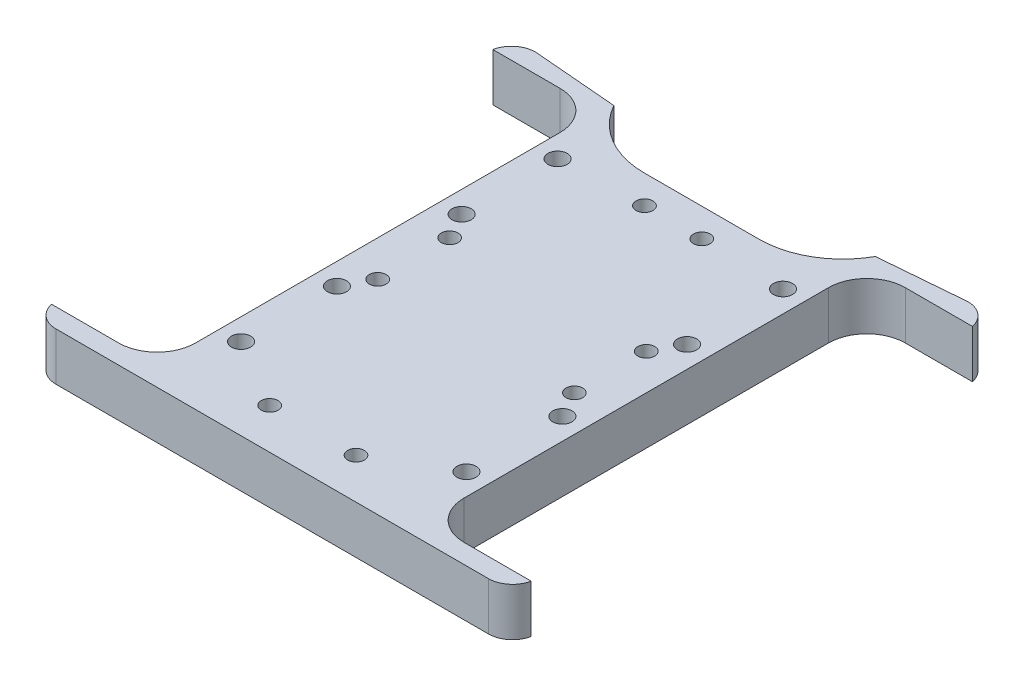
SolidWorks part; units mm, degrees
material "PET"
ref_plane "Front Plane" through (0, 0, 0) normal (0, 0, 1) x (1, 0, 0)
ref_plane "Top Plane" through (0, 0, 0) normal (0, 1, 0) x (1, 0, 0)
ref_plane "Right Plane" through (0, 0, 0) normal (1, 0, 0) x (0, 0, -1)
sketch "Sketch2" plane through (0, 0, 0) normal (0, 1, 0) x (1, 0, 0)
  line L0 (-50, 0) -> (50, 0) construction
  line L1 (0, -50) -> (0, 50) construction
  line L2 (-50, 50) -> (-28, 50)
  line L3 (-50, -50) -> (-50, -46)
  line L4 (50, -50) -> (50, -46)
  line L5 (-50, -50) -> (50, -50)
  line L7 (-11.961, 39.5) -> (11.961, 39.5)
  line L9 (28, 50) -> (50, 50)
  line L10 (-50, 46) -> (-36, 46)
  line L11 (-28, 38) -> (-28, -38)
  line L12 (-50, -46) -> (-36, -46)
  line L13 (-50, 46) -> (-50, 50)
  line L14 (50, -46) -> (36, -46)
  line L15 (28, 38) -> (28, -38)
  line L16 (50, 46) -> (36, 46)
  line L17 (50, 46) -> (50, 50)
  line L18 (-50, 46) -> (-50, 0) construction
  line L19 (-50, 23) -> (64.666, 23) construction
  line L20 (-50, 0) -> (-50, -46) construction
  line L21 (-50, -23) -> (40.4049, -23) construction
  arc A1 (28, 50) -> (11.961, 39.5) centre (11.961, 57) cw
  arc A2 (-28, 50) -> (-11.961, 39.5) centre (-11.961, 57) ccw
  arc A3 (-28, -38) -> (-36, -46) centre (-36, -38) cw
  arc A4 (-36, 46) -> (-28, 38) centre (-36, 38) cw
  arc A5 (28, -38) -> (36, -46) centre (36, -38) ccw
  arc A6 (36, 46) -> (28, 38) centre (36, 38) ccw
  circle A7 centre (-23.5, 33) radius 2
  circle A8 centre (-23.5, 13) radius 2
  circle A9 centre (23.5, 33) radius 2
  circle A10 centre (23.5, 13) radius 2
  circle A11 centre (-23.5, -33) radius 2
  circle A12 centre (23.5, -33) radius 2
  circle A13 centre (23.5, -13) radius 2
  circle A14 centre (-23.5, -13) radius 2
  circle A15 centre (-20.5, 7.5) radius 1.75
  circle A17 centre (20.5, 7.5) radius 1.75
  circle A18 centre (20.5, -7.5) radius 1.75
  circle A19 centre (-20.5, -7.5) radius 1.75
  point P8 (0, 0)
  point P11 (0, 50)
  point P13 (-50, 0)
  point P16 (50, 0)
  point P17 (0, 39.5)
  point P19 (0, -50)
  dimension "D8" = 17.5
  dimension "D9" = 4
  dimension "D5" = 17.5
  dimension "D11" = 8
  dimension "D15" = 4
  dimension "D16" = 4.5
  dimension "D18" = 3.5
  dimension "D4" = 100
  dimension "D6" = 56
  dimension "D7" = 10.5
  dimension "D10" = 4
  dimension "D12" = 50
  dimension "D14" = 23
  dimension "D17" = 10
  dimension "D19" = 7.5
  dimension "D20" = 7.5
extrude "Boss-Extrude1" add sketch "Sketch2" along normal blind 10 contours A6 L16 L17 L9 A1 L7 A2 L2 L13 L10 A4 L11 A3 L12 L3 L5 L4 L14 A5 L15 A17 A15 A14 A11 A10 A8 A7 A9 A12 A13 A18 A19 region at (0, 0, 4.1546)
fillet "Fillet1" radius 5 4 edges at (50, 5, 50) (-50, 5, 50) (-50, 5, -50) (50, 5, -50)
sketch "Sketch4" plane through (0, 10, 0) normal (0, 1, 0) x (1, 0, 0)
  line L0 (45.101, 50) -> (27.258, 48.5)
  line L1 (-45.101, 50) -> (-27.258, 48.5)
  line L2 (-45.101, 50) -> (-28, 50) construction
  line L3 (28, 50) -> (45.101, 50) construction
  line L4 (28, 50) -> (45.101, 50)
  line L5 (-45.101, 50) -> (-28, 50)
  arc A0 (11.961, 39.5) -> (28, 50) centre (11.961, 57) ccw construction
  arc A1 (-28, 50) -> (-11.961, 39.5) centre (-11.961, 57) ccw construction
  arc A2 (27.258, 48.5) -> (28, 50) centre (11.961, 57) ccw
  arc A3 (-28, 50) -> (-27.258, 48.5) centre (-11.961, 57) ccw
  dimension "D1" = 1.5
  dimension "D2" = 1.5
extrude "Cut-Extrude1" cut sketch "Sketch4" against normal blind 15
sketch "Sketch5" plane through (0, 10, 0) normal (0, 1, 0) x (1, 0, 0)
  circle A0 centre (9, -41.5315) radius 1.75
  circle A1 centre (-9, -41.5315) radius 1.75
  circle A2 centre (5.9805, 33.6) radius 1.75
  circle A3 centre (-5.9805, 33.6) radius 1.75
  dimension "D1" = 3.5
  dimension "D2" = 3.5
  dimension "D3" = 3.5
  dimension "D4" = 3.5
extrude "Cut-Extrude2" cut sketch "Sketch5" against normal up to surface (10 mm away) and the other way through all up to face at (20.5, 0, -5.75)
